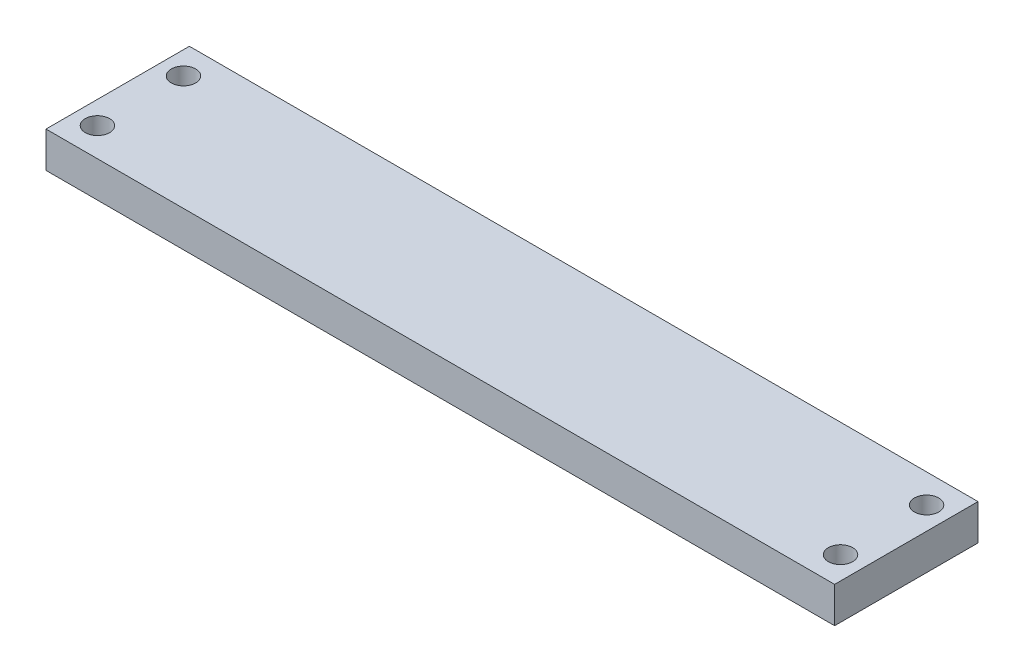
SolidWorks part; units mm, degrees
ref_plane "Front Plane" through (0, 0, 0) normal (0, 0, 1) x (1, 0, 0)
ref_plane "Top Plane" through (0, 0, 0) normal (0, 1, 0) x (1, 0, 0)
ref_plane "Right Plane" through (0, 0, 0) normal (1, 0, 0) x (0, 0, -1)
sketch "Sketch1" plane through (0, 0, 0) normal (0, 1, 0) x (1, 0, 0)
  line L5 (-55, -10) -> (55, -10)
  line L6 (-55, -10) -> (-55, 10)
  line L7 (-55, 10) -> (55, 10)
  line L8 (55, -10) -> (55, 10)
  line L9 (0, 10) -> (0, -10) construction
  line L10 (-55, 0) -> (55, 0) construction
  point P0 (0, 0)
  dimension "D1" = 20
  dimension "D2" = 110
extrude "Boss-Extrude1" add sketch "Sketch1" along normal mid plane 5
sketch "Sketch2" plane through (0, 2.5, 0) normal (0, 1, 0) x (1, 0, 0)
  line L0 (0, 10) -> (0, -10) construction
  line L1 (55, 10) -> (-55, 10) construction
  line L2 (-55, -10) -> (55, -10) construction
  line L3 (-55, 0) -> (55, 0) construction
  line L4 (-55, 10) -> (-55, -10) construction
  line L5 (55, -10) -> (55, 10) construction
  point P12 (-51.825, -6)
  point P14 (51.825, -6)
  point P16 (-51.825, 6)
  point P17 (51.825, 6)
  dimension "D1" = 103.65
  dimension "D2" = 4
hole_wizard "M3 Clearance Hole1" positions "Sketch2" profile "Sketch3" hole size "M3" standard "ANSI Metric" end condition through all
sketch "Sketch3" plane through (51.825, 2.5, -6) normal (1, 0, 0) x (0, 0, 1)
  line L0 (0, 0) -> (0, 5)
  line L1 (0, 5) -> (1.7, 5)
  line L2 (1.7, 5) -> (1.7, 0)
  line L5 (1.7, 0) -> (0, 0)
  line L11 (0, -6.35) -> (0, 107.95) construction
  dimension "Thru Hole Dia." = 3.4
  dimension "Thru Hole Depth" = 5
